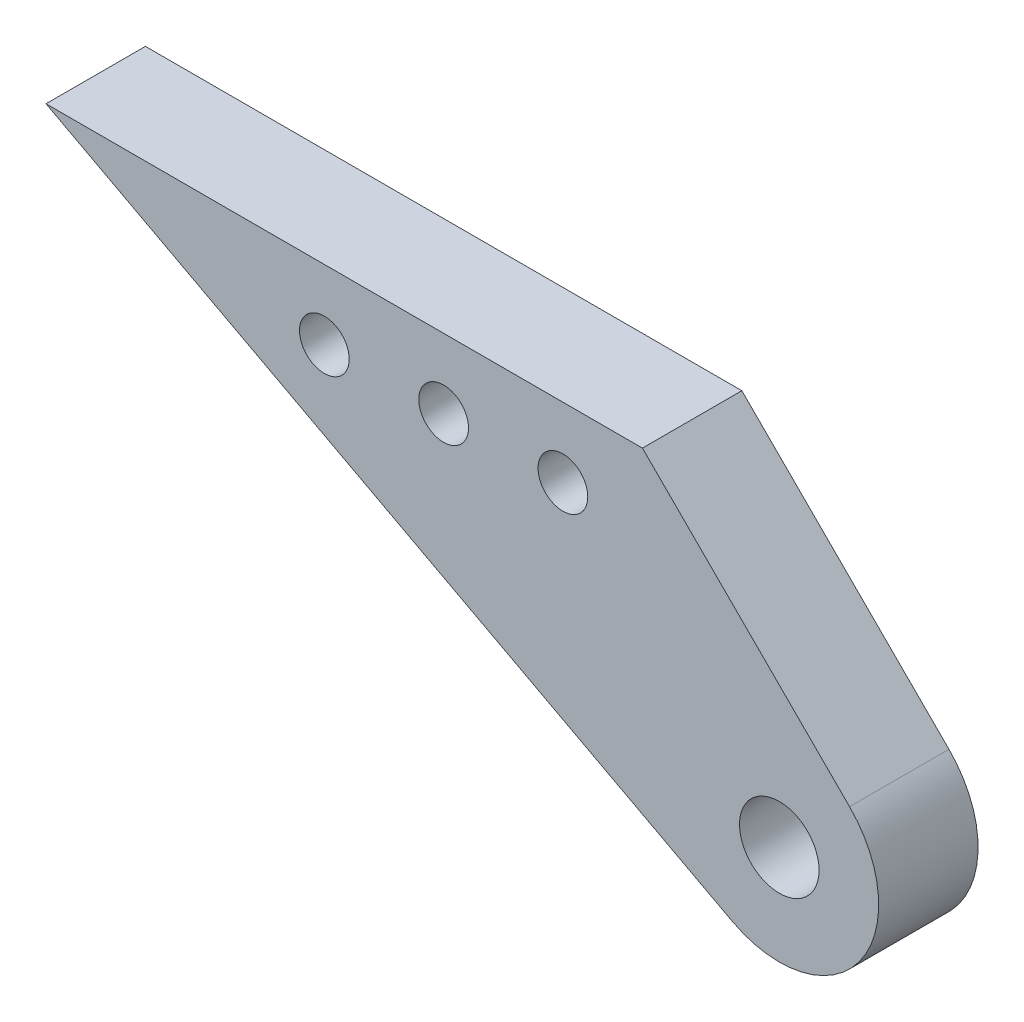
SolidWorks part; units mm, degrees
ref_plane "前视基准面" through (0, 0, 0) normal (0, 0, 1) x (1, 0, 0)
ref_plane "上视基准面" through (0, 0, 0) normal (0, 1, 0) x (1, 0, 0)
ref_plane "右视基准面" through (0, 0, 0) normal (1, 0, 0) x (0, 0, -1)
other "Configuration Table"
sketch "草图2" plane through (0, 0, 0) normal (0, 0, 1) x (1, 0, 0)
  line L0 (-30, 0) -> (0, 0)
  line L2 (4.536, -18.3631) -> (-30, 0)
  line L5 (0, 0) -> (10.4179, -10.4118)
  circle A2 centre (-4, -3.5) radius 1.25
  arc A3 (4.536, -18.3631) -> (10.4179, -10.4118) centre (6.8834, -13.9484) ccw
  circle A4 centre (6.8834, -13.9484) radius 2
  circle A5 centre (-10, -3.5) radius 1.25
  circle A6 centre (-16, -3.5) radius 1.25
  point P3 (9.0659, -12.6998)
  point P5 (11.2082, -16.2479)
  point P13 (7.6335, -14.3472)
  point P14 (6.8834, -13.9484)
  dimension "D5" = 2.5
  dimension "D6" = 3
  dimension "D4" = 3.5
  dimension "D8" = 4
  dimension "D9" = 5
  dimension "D1" = 4
  dimension "D2" = 28
  dimension "D3" = 30
extrude "凸台-拉伸1" add sketch "草图2" along normal blind 5
